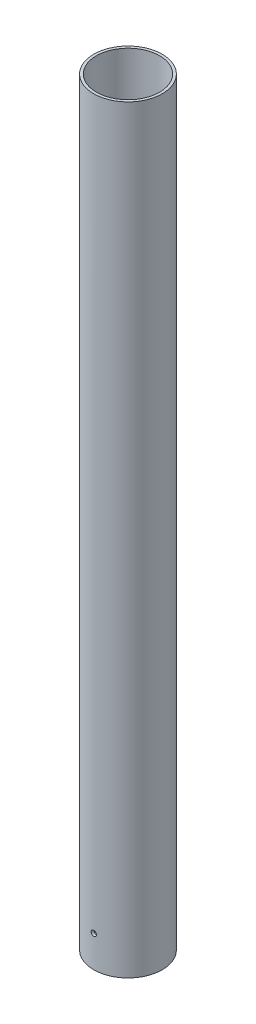
SolidWorks part; units mm, degrees
material "Cardboard Tube"
ref_plane "Front Plane" through (0, 0, 0) normal (0, 0, 1) x (1, 0, 0)
ref_plane "Top Plane" through (0, 0, 0) normal (0, 1, 0) x (1, 0, 0)
ref_plane "Right Plane" through (0, 0, 0) normal (1, 0, 0) x (0, 0, -1)
sketch "Sketch1" plane through (0, 0, 0) normal (0, 1, 0) x (1, 0, 0)
  circle A0 centre (0, 0) radius 38.1
  circle A1 centre (0, 0) radius 41.275
  dimension "D1" = 3.175
  dimension "D2" = 76.2
extrude "Boss-Extrude1" add sketch "Sketch1" along normal blind 914.4
sketch "Sketch2" plane through (0, 0, 0) normal (0, 0, 1) x (1, 0, 0)
  line L0 (-41.275, 0) -> (41.275, 0) construction
  circle A0 centre (0, 38.1) radius 3.175
  dimension "D1" = 38.1
  dimension "D2" = 6.35
extrude "Cut-Extrude1" cut sketch "Sketch2" against normal through all both and the other way through all
